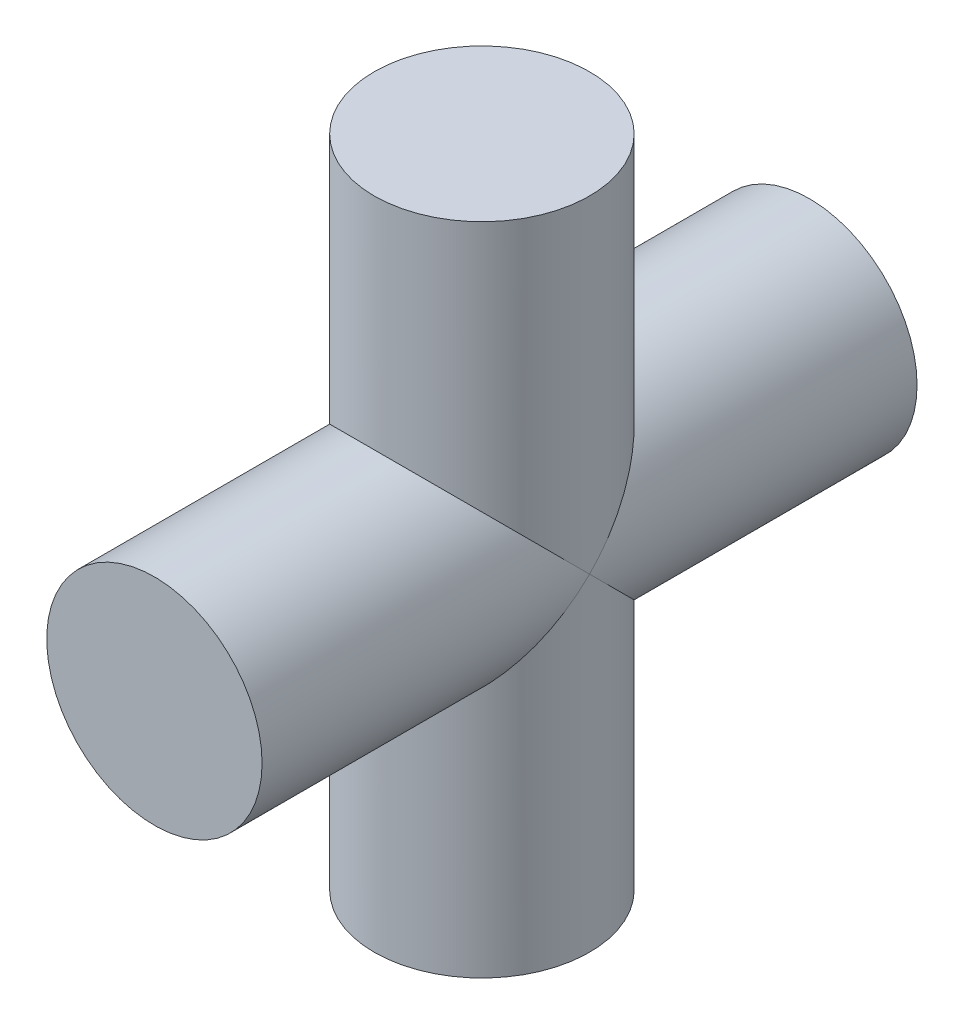
SolidWorks part; units mm, degrees
ref_plane "Front Plane" through (0, 0, 0) normal (0, 0, 1) x (1, 0, 0)
ref_plane "Top Plane" through (0, 0, 0) normal (0, 1, 0) x (1, 0, 0)
ref_plane "Right Plane" through (0, 0, 0) normal (1, 0, 0) x (0, 0, -1)
sketch "Sketch1" plane through (0, 0, 0) normal (0, 1, 0) x (1, 0, 0)
  circle A0 centre (0, 0) radius 12
  dimension "D1" = 24
extrude "Boss-Extrude1" add sketch "Sketch1" along normal blind 73
sketch "Sketch2" plane through (0, 0, 0) normal (0, 0, 1) x (1, 0, 0)
  line L0 (0, 0) -> (0, 36.5) construction
  line L1 (0, 36.5) -> (0, 73) construction
  line L2 (12, 73) -> (-12, 73) construction
  circle A0 centre (0, 36.5) radius 12
  dimension "D1" = 24
extrude "Boss-Extrude2" add sketch "Sketch2" along normal blind 36.5 and the other way blind 36.5
